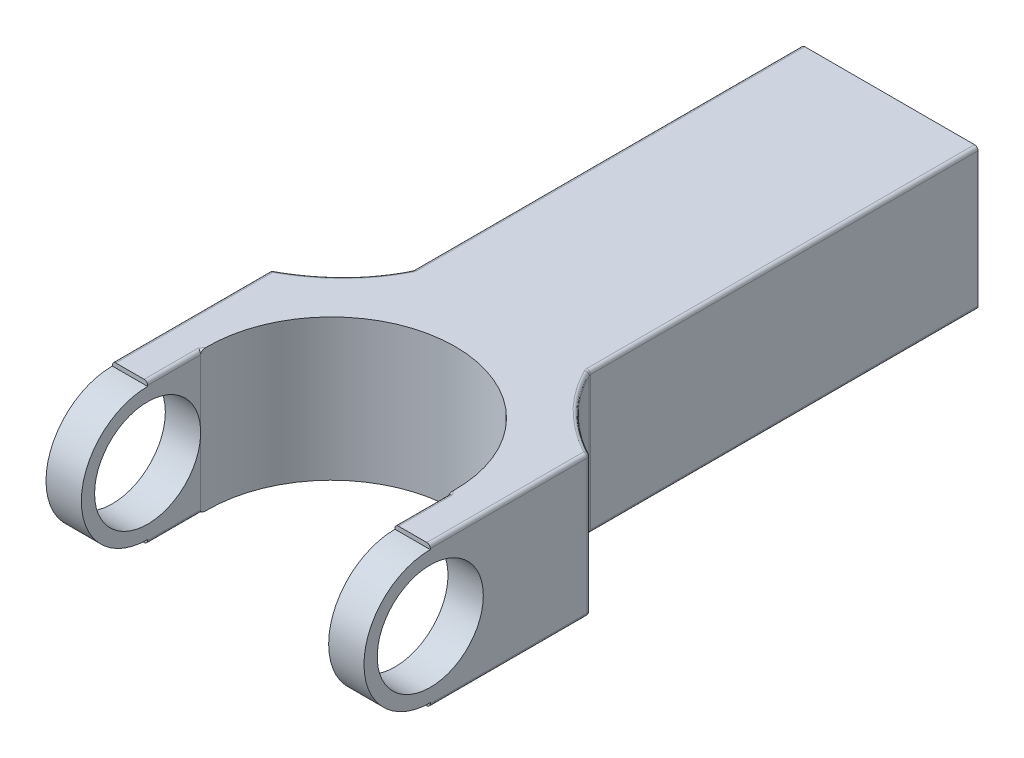
SolidWorks part; units mm, degrees
ref_plane "Front Plane" through (0, 0, 0) normal (0, 0, 1) x (1, 0, 0)
ref_plane "Top Plane" through (0, 0, 0) normal (0, 1, 0) x (1, 0, 0)
ref_plane "Right Plane" through (0, 0, 0) normal (1, 0, 0) x (0, 0, -1)
sketch "Sketch1" plane through (0, 0, 0) normal (0, 1, 0) x (1, 0, 0)
  line L0 (0, 59.9516) -> (0, 199.8387)
  line L1 (49.9597, 249.8387) -> (49.9597, 319.8387)
  line L2 (49.9597, 199.8387) -> (49.9597, 100.1104)
  line L3 (89.9274, -59.9516) -> (89.9274, -29.9516)
  line L4 (89.9274, 59.9516) -> (89.9274, -69.9436)
  line L5 (89.9274, -69.9436) -> (69.9436, -69.9436)
  line L6 (69.9436, 0) -> (69.9436, -69.9436)
  line L7 (89.9274, -69.9436) -> (89.9274, -59.9516)
  line L8 (89.9274, 0) -> (89.9274, 59.9516)
  line L10 (49.9597, 319.8387) -> (0, 319.8387)
  line L12 (0, 199.8387) -> (0, 249.8387)
  line L14 (49.9597, 199.8387) -> (49.9597, 249.8387)
  line L15 (49.9597, 319.8387) -> (49.9597, 249.8387)
  line L17 (0, 319.8387) -> (0, 249.8387)
  line L18 (89.9274, -29.9516) -> (89.9274, 0.0484)
  spline S0 degree 2 poles (89.9274, 59.9516) (62.3911, 74.8404) (49.9597, 100.1104) knots 0 0 0 0.899079 0.899079 0.899079
  spline S1 degree 2 poles (69.9436, 0) (40.212, 38.7673) (-1.1042, 60.5376) knots 0 0 0 1 1 1
  point P10 (89.9274, 0)
  dimension "D1" = 50
extrude "Boss-Extrude4" add sketch "Sketch1" along normal blind 80 contours S1 L6 L5 L4 L3 L8 S0 L2 L14 L1 L10 L17 L12 L0 region at (36.5328, 0, -142.873)
sketch "Sketch7" plane through (89.9274, 0, 0) normal (1, 0, 0) x (0, 0, -1)
  line L0 (-69.9436, 40) -> (-29.9436, 40)
  line L1 (-69.9436, 80) -> (-69.9436, 0) construction
  circle A0 centre (-29.9436, 40) radius 30
extrude "Cut-Extrude5" cut sketch "Sketch7" against normal mid plane 80 contours A0
mirror "Mirror2" about plane through (0, 80, 0) normal (1, 0, 0) of bodies 110
fillet "Fillet2" radius 2 24 edges at (49.9597, 0, -209.9745) (49.9597, 80, -209.9745) (-49.9597, 0, -209.9745) (-49.9597, 80, -209.9745) (89.9274, 0, 4.996) (89.9274, 80, 4.996) (-89.9274, 0, 4.996) (-89.9274, 80, 4.996) (69.9436, 80, 34.9718) (-69.9436, 80, 34.9718) (-69.9436, 0, 34.9718) (69.9436, 0, 34.9718) (-49.9597, 40, -100.1104) (-89.9274, 40, -59.9516) (49.9597, 40, -100.1104) (89.9274, 40, -59.9516)
sketch "Sketch8" plane through (89.9274, 0, 0) normal (1, 0, 0) x (0, 0, -1)
  line L0 (-69.9436, 78) -> (-69.9436, 2) construction
  line L1 (-109.9436, -1.986) -> (-29.9436, -1.986)
  line L2 (-109.9436, -1.986) -> (-109.9436, 81.986)
  line L3 (-109.9436, 81.986) -> (-29.9436, 81.986)
  line L4 (-29.9436, -1.986) -> (-29.9436, 2.5)
  line L5 (-109.9436, -1.986) -> (-29.9436, 81.986) construction
  line L6 (-109.9436, 81.986) -> (-29.9436, -1.986) construction
  line L7 (-29.9436, 77.5) -> (-29.9436, 81.986)
  arc A0 (-29.9436, 77.5) -> (-29.9436, 2.5) centre (-29.9436, 40) ccw
  point P3 (-69.9436, 40)
extrude "Cut-Extrude6" cut sketch "Sketch8" against normal mid plane 610
sketch "Sketch9" plane through (0, 80, 0) normal (0, 1, 0) x (1, 0, 0)
  line L0 (-69.9436, 0) -> (69.9436, 0)
  arc A0 (-69.9436, 0) -> (69.9436, 0) centre (0, -4.3463) cw
extrude "Cut-Extrude7" cut sketch "Sketch9" against normal mid plane 610
sketch "Sketch10" plane through (0, 80, 0) normal (0, 1, 0) x (1, 0, 0)
  line L0 (71.9436, 0.6786) -> (69.9436, 0) construction
  line L1 (-69.9436, 0) -> (69.9436, 0)
  arc A0 (-69.9436, 0) -> (69.9436, 0) centre (0, 4.0419) cw
  arc A1 (69.9436, 0) -> (69.6174, 3.6792) centre (0, -4.3463) ccw construction
extrude "Cut-Extrude8" cut sketch "Sketch10" against normal mid plane 610
